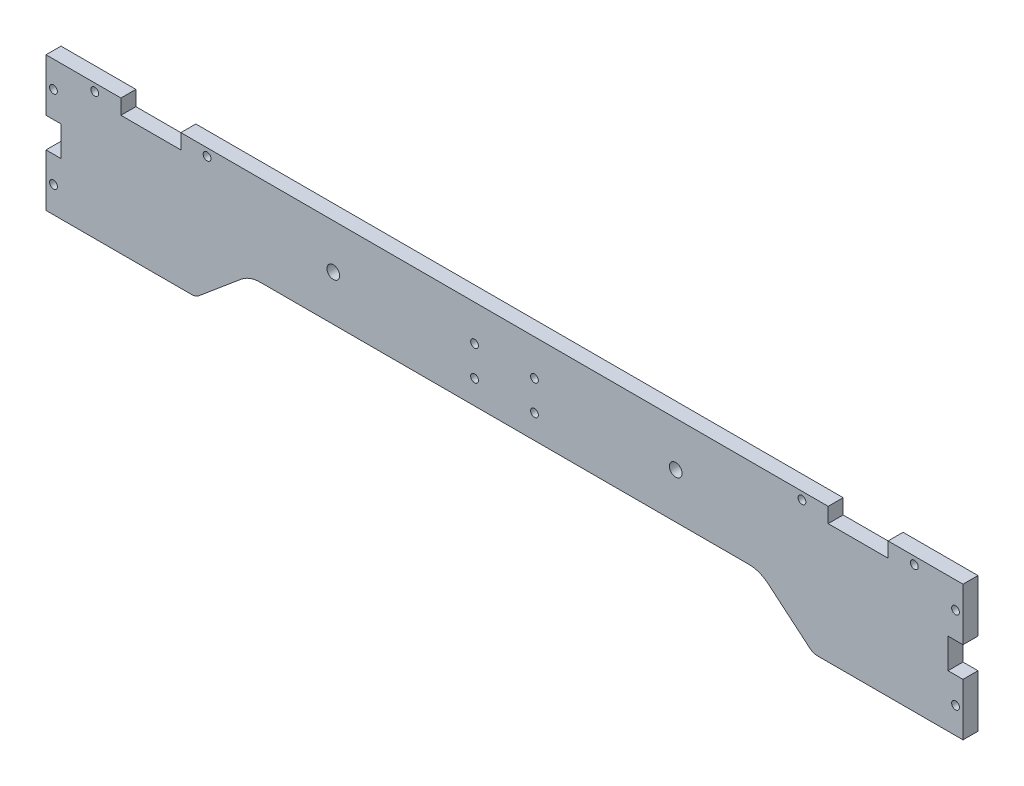
SolidWorks part; units mm, degrees
material "Pine"
ref_plane "Front Plane" through (0, 0, 0) normal (0, 0, 1) x (1, 0, 0)
ref_plane "Top Plane" through (0, 0, 0) normal (0, 1, 0) x (1, 0, 0)
ref_plane "Right Plane" through (0, 0, 0) normal (1, 0, 0) x (0, 0, -1)
ref_plane "Plane1" through (0, 0, 222.25) normal (0, 0, 1) x (1, 0, 0)
sketch "Sketch1" plane through (0, 0, 222.25) normal (0, 0, 1) x (1, 0, 0)
  line L0 (-25.4, 57.15) -> (-25.4, 50.8)
  line L1 (-25.4, 50.8) -> (-50.8, 50.8)
  line L2 (-50.8, 50.8) -> (-50.8, 57.15)
  line L3 (-50.8, 57.15) -> (-325.12, 57.15)
  line L4 (-325.12, 57.15) -> (-325.12, 50.8)
  line L5 (-325.12, 50.8) -> (-350.52, 50.8)
  line L6 (-350.52, 50.8) -> (-350.52, 57.15)
  line L7 (-350.52, 57.15) -> (-382.27, 57.15)
  line L8 (-382.27, 57.15) -> (-382.27, 34.925)
  line L9 (-382.27, 34.925) -> (-375.92, 34.925)
  line L10 (-375.92, 34.925) -> (-375.92, 22.225)
  line L11 (-375.92, 22.225) -> (-382.27, 22.225)
  line L12 (-382.27, 22.225) -> (-382.27, 0)
  line L13 (-382.27, 0) -> (-320.619, 0)
  line L14 (-317.3536, 1.1885) -> (-299.6081, 16.0788)
  line L15 (-291.4447, 19.05) -> (-84.4753, 19.05)
  line L16 (-76.3119, 16.0788) -> (-58.5664, 1.1885)
  line L17 (-55.301, 0) -> (6.35, 0)
  line L18 (6.35, 0) -> (6.35, 22.225)
  line L19 (6.35, 22.225) -> (0, 22.225)
  line L20 (0, 22.225) -> (0, 34.925)
  line L21 (0, 34.925) -> (6.35, 34.925)
  line L22 (6.35, 34.925) -> (6.35, 57.15)
  line L23 (6.35, 57.15) -> (-25.4, 57.15)
  circle A0 centre (-379.095, 11.1125) radius 1.65
  circle A1 centre (3.175, 11.1125) radius 1.65
  circle A2 centre (-379.095, 46.0375) radius 1.65
  circle A3 centre (3.175, 46.0375) radius 1.65
  circle A4 centre (-175.26, 41.91) radius 1.65
  circle A5 centre (-200.66, 41.91) radius 1.65
  circle A6 centre (-175.26, 29.21) radius 1.65
  circle A7 centre (-200.66, 29.21) radius 1.65
  circle A8 centre (-14.2875, 53.975) radius 1.65
  circle A9 centre (-361.6325, 53.975) radius 1.65
  circle A10 centre (-61.9125, 53.975) radius 1.65
  circle A11 centre (-314.0075, 53.975) radius 1.65
  circle A12 centre (-115.41, 38.26) radius 2.7
  circle A13 centre (-260.51, 38.26) radius 2.7
  arc A14 (-320.619, 0) -> (-317.3536, 1.1885) centre (-320.619, 5.08) ccw
  arc A15 (-299.6081, 16.0788) -> (-291.4447, 19.05) centre (-291.4447, 6.35) cw
  arc A16 (-84.4753, 19.05) -> (-76.3119, 16.0788) centre (-84.4753, 6.35) cw
  arc A17 (-58.5664, 1.1885) -> (-55.301, 0) centre (-55.301, 5.08) ccw
extrude "Boss-Extrude1" add sketch "Sketch1" against normal blind 6.35
